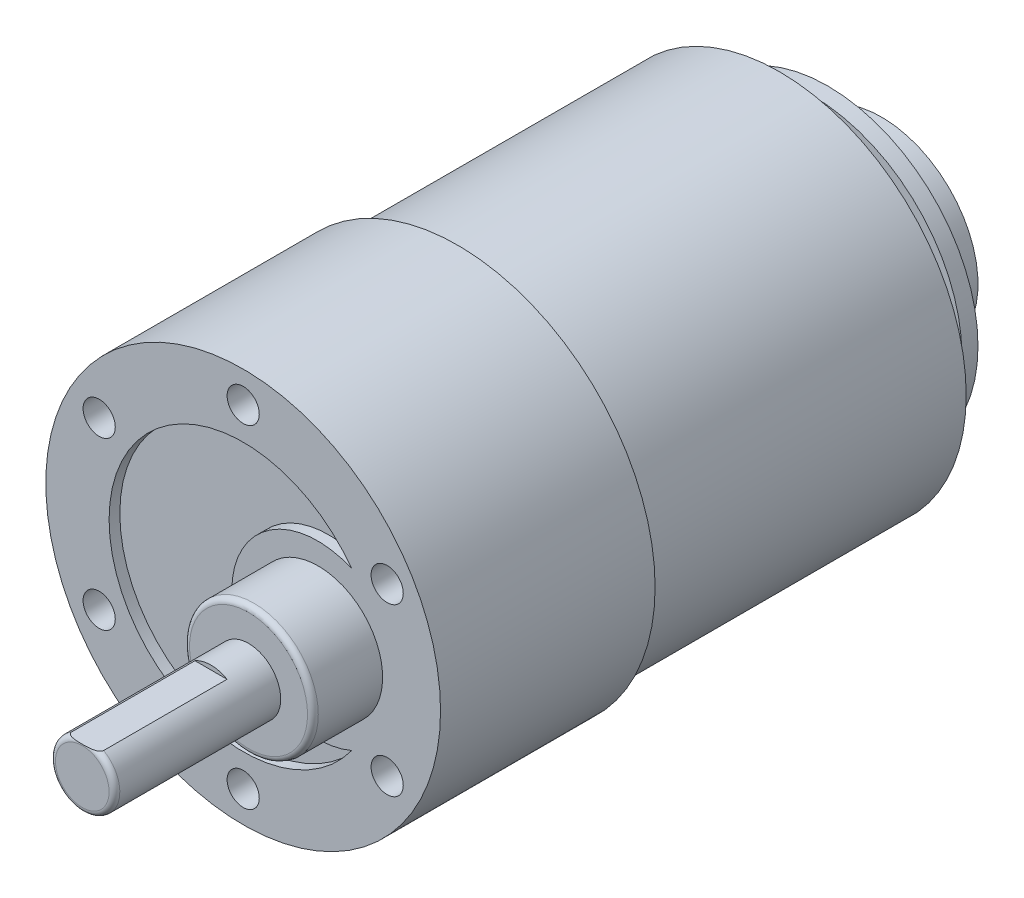
SolidWorks part; units mm, degrees
ref_plane "Front Plane" through (0, 0, 0) normal (0, 0, 1) x (1, 0, 0)
ref_plane "Top Plane" through (0, 0, 0) normal (0, 1, 0) x (1, 0, 0)
ref_plane "Right Plane" through (0, 0, 0) normal (1, 0, 0) x (0, 0, -1)
sketch "Sketch1" plane through (0, 0, 0) normal (0, 0, 1) x (1, 0, 0)
  circle A0 centre (0, 0) radius 18.4
  dimension "D1" = 36.8
extrude "Boss-Extrude1" add sketch "Sketch1" along normal blind 20
sketch "Sketch2" plane through (0, 0, 0) normal (0, 0, -1) x (-1, 0, 0)
  circle A0 centre (0, 0) radius 17.4
  dimension "D1" = 34.8
extrude "Boss-Extrude2" add sketch "Sketch2" along normal blind 30
sketch "Sketch3" plane through (0, 0, 20) normal (0, 0, 1) x (1, 0, 0)
  circle A0 centre (7, 0) radius 6
  dimension "D1" = 12
  dimension "D2" = 7
extrude "Boss-Extrude3" add sketch "Sketch3" along normal blind 6.5
fillet "Fillet1" radius 0.5 1 edges at (13, 0, 26.5)
sketch "Sketch4" plane through (0, 0, 26.5) normal (0, 0, 1) x (1, 0, 0)
  line L0 (7, -6.8172) -> (7, 7.1125) construction
  circle A0 centre (7, 0) radius 3
  dimension "D1" = 6
extrude "Boss-Extrude4" add sketch "Sketch4" along normal blind 15.5
sketch "Sketch5" plane through (0, 0, 42) normal (0, 0, 1) x (1, 0, 0)
  line L0 (5.5033, 2.6) -> (8.4967, 2.6)
  line L1 (7, -3) -> (9.3109, -3) construction
  circle A0 centre (7, 0) radius 3 construction
  circle A1 centre (7, 0) radius 3 construction
  arc A2 (8.4967, 2.6) -> (5.5033, 2.6) centre (7, 0) ccw
  dimension "D1" = 5.6
extrude "Cut-Extrude1" cut sketch "Sketch5" against normal blind 12
hole_wizard "Ø3.0 (3) Diameter Hole1" positions "Sketch7" profile "Sketch6" hole size "Ø3.0" standard "Ansi Metric"
sketch "Sketch7" plane through (0, 0, 20) normal (0, 0, 1) x (1, 0, 0)
  point P0 (-13.4234, 7.75)
  point P1 (-13.4234, -7.75)
  point P3 (0, -15.5)
  point P5 (13.4234, 7.75)
  point P7 (0, 15.5)
  point P22 (13.4234, -7.75)
  dimension "D1" = 15.5
  dimension "D2" = 15.5
  dimension "D3" = 15.5
  dimension "D4" = 15.5
  dimension "D5" = 15.5
  dimension "D6" = 15.5
  dimension "D7" = 15.5
  dimension "D8" = 15.5
  dimension "D9" = 15.5
  dimension "D10" = 15.5
sketch "Sketch6" plane through (-13.4234, 7.75, 20) normal (1, 0, 0) x (0, -1, 0)
  line L0 (0, 0) -> (0, 3.9013)
  line L1 (0, 3.9013) -> (1.5, 3)
  line L2 (1.5, 3) -> (1.5, 0)
  line L5 (1.5, 0) -> (0, 0)
  line L10 (0, 3.9013) -> (-1.5, 3) construction
  line L11 (0, -6.35) -> (0, 107.95) construction
  dimension "Hole Dia." = 3
  dimension "Hole Depth" = 3
  dimension "Drill Angle" = 118
sketch "Sketch8" plane through (0, 0, 20) normal (0, 0, 1) x (1, 0, 0)
  line L0 (-0.5907, 0) -> (14.4711, 0) construction
  line L1 (7, 7.3586) -> (7, -7.457) construction
  arc A0 (10.1162, 7.3426) -> (10.1162, -7.3426) centre (0, 0) ccw
  arc A1 (10.1162, 7.3426) -> (10.1162, -7.3426) centre (6.9402, 0) ccw
  dimension "D1" = 25
  dimension "D2" = 16
extrude "Cut-Extrude2" cut sketch "Sketch8" against normal blind 1
sketch "Sketch9" plane through (0, 0, -30) normal (0, 0, -1) x (-1, 0, 0)
  circle A0 centre (0, 0) radius 4
  dimension "D1" = 8
extrude "Boss-Extrude5" add sketch "Sketch9" along normal blind 1
fillet "Fillet2" radius 0.5 1 edges at (-4, 0, -31)
ref_plane "Plane1" through (0, 0, -33) normal (0, 0, -1) x (-1, 0, 0)
sketch "Sketch10" plane through (0, 0, -33) normal (0, 0, -1) x (-1, 0, 0)
  circle A0 centre (0, 0) radius 14
  dimension "D1" = 28
extrude "Boss-Extrude6" add sketch "Sketch10" along normal blind 1.5 separate body
sketch "Sketch11" plane through (0, 0, -30) normal (0, 0, -1) x (-1, 0, 0)
  line L0 (0, 11.55) -> (0, 12.55) construction
  line L1 (-1.75, 12.55) -> (1.75, 12.55)
  line L2 (-1.75, 12.55) -> (-1.75, 11.55)
  line L3 (-1.75, 11.55) -> (1.75, 11.55)
  line L4 (1.75, 12.55) -> (1.75, 11.55)
  line L5 (-1.75, 12.05) -> (1.75, 12.05) construction
  line L6 (-3.5, 0) -> (3.5, 0) construction
  line L7 (1.75, -12.55) -> (1.75, -11.55)
  line L8 (-1.75, -12.55) -> (-1.75, -11.55)
  line L9 (-1.75, -12.55) -> (1.75, -12.55)
  line L10 (-1.75, -11.55) -> (1.75, -11.55)
  circle A0 centre (0, 0) radius 3.5 construction
  dimension "D1" = 3.5
  dimension "D2" = 1
  dimension "D3" = 12.05
extrude "Boss-Extrude7" add sketch "Sketch11" along normal blind 5.6
fillet "Fillet3" radius 0.5 4 edges at (-1.75, -12.05, -35.6) (1.75, -12.05, -35.6) (-1.75, 12.05, -35.6) (1.75, 12.05, -35.6)
ref_plane "Plane2" through (0, 0, -36.5) normal (0, 0, -1) x (-1, 0, 0)
sketch "Sketch13" plane through (0, 0, -36.5) normal (0, 0, -1) x (-1, 0, 0)
  circle A0 centre (0, 0) radius 9
  dimension "D1" = 18
extrude "Boss-Extrude8" add sketch "Sketch13" along normal blind 3 separate body
sketch "Sketch14" plane through (0, 0, -31) normal (0, 0, -1) x (-1, 0, 0)
  circle A0 centre (0, 0) radius 1.5
  dimension "D1" = 3
extrude "Boss-Extrude9" add sketch "Sketch14" along normal blind 8.55
fillet "Fillet4" radius 0.5 1 edges at (7, -3, 42)
